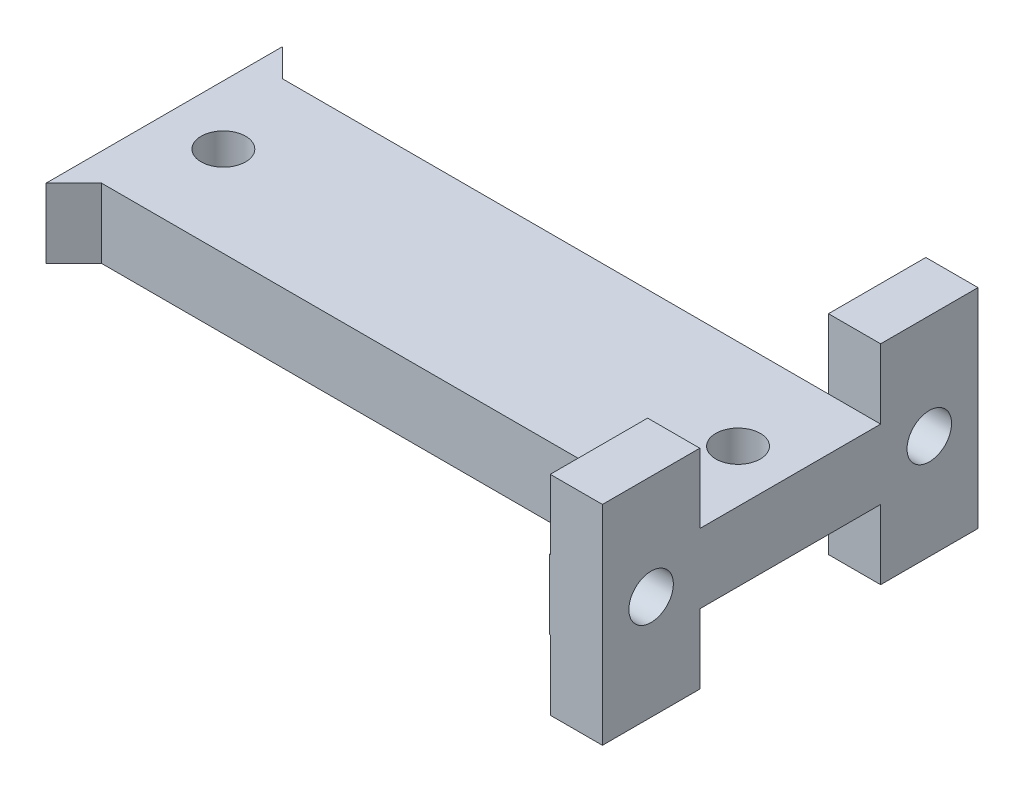
SolidWorks part; units mm, degrees
ref_plane "前视基准面" through (0, 0, 0) normal (0, 0, 1) x (1, 0, 0)
ref_plane "上视基准面" through (0, 0, 0) normal (0, 1, 0) x (1, 0, 0)
ref_plane "右视基准面" through (0, 0, 0) normal (1, 0, 0) x (0, 0, -1)
sketch "草图1" plane through (0, 0, 0) normal (0, 1, 0) x (1, 0, 0)
  line L0 (0, 0) -> (0, -100)
  line L1 (0, 0) -> (100, 0)
  line L2 (100, 0) -> (100, -100)
  line L3 (100, -100) -> (0, -100)
  dimension "D1" = 100
extrude "凸台-拉伸1" add sketch "草图1" along normal blind 10
sketch "草图2" plane through (0, 10, 0) normal (0, 1, 0) x (1, 0, 0)
  line L0 (20.6546, -10.25) -> (20.6546, -13)
  line L1 (20.6546, -13) -> (50.1546, -13)
  line L2 (50.1546, -13) -> (50.1546, -10.25)
  line L3 (50.1546, -10.25) -> (53.9046, -10.25)
  line L4 (16.9046, -2.75) -> (20.6546, -2.75)
  line L5 (20.6546, -2.75) -> (20.6546, 0)
  line L6 (100, 0) -> (0, 0) construction
  line L7 (20.6546, 0) -> (20.6546, -2.75) construction
  line L8 (20.6546, 0) -> (50, 0)
  line L9 (50, 0) -> (50.1546, -2.75)
  line L10 (50.1546, -2.75) -> (53.9046, -2.75)
  line L11 (16.9046, -10.25) -> (20.6546, -10.25)
  line L12 (20.6546, 0) -> (0, 0)
  line L13 (0, 0) -> (0, -100)
  line L14 (0, -100) -> (100, -100)
  line L15 (100, -100) -> (100, 0)
  line L16 (100, 0) -> (50, 0)
  line L17 (20.6546, -13) -> (0, -13)
  line L18 (50.1546, -13) -> (100, -13)
  line L19 (100, -13) -> (100, -100)
  arc A0 (53.9046, -10.25) -> (53.9046, -2.75) centre (53.9046, -6.5) ccw
  arc A1 (16.9046, -2.75) -> (16.9046, -10.25) centre (16.9046, -6.5) ccw
  line M3 (0, -100) -> (100, -100)
  line M4 (100, -100) -> (100, 0)
extrude "切除-拉伸3" cut sketch "草图2" against normal blind 27 contours L18 L1 L17 L13 M3 M4 region at (50, 10, 56.5)
sketch "草图4" plane through (0, 10, 0) normal (0, 1, 0) x (1, 0, 0)
  line L0 (16.9046, -6.5) -> (13.1546, -6.5)
  line L1 (13.1546, -6.5) -> (13.1546, 0)
  line L2 (100, 0) -> (0, 0) construction
  line L3 (13.1546, 0) -> (13.1546, -13)
  line L4 (0, -13) -> (100, -13) construction
  line L5 (53.9046, -6.5) -> (57.6546, -6.5)
  line L6 (57.6546, -6.5) -> (57.6546, -13)
  line L7 (57.6546, -13) -> (57.6546, 0)
  line L8 (57.6546, 0) -> (100, 0)
  line L9 (100, 0) -> (100, -13)
  line L10 (100, -13) -> (57.6546, -13)
  line L11 (13.1546, -13) -> (0, -13)
  line L12 (0, -13) -> (0, 0)
  line L13 (0, 0) -> (13.1546, 0)
  arc A0 (16.9046, -2.75) -> (16.9046, -10.25) centre (16.9046, -6.5) ccw construction
  arc A1 (53.9046, -10.25) -> (53.9046, -2.75) centre (53.9046, -6.5) ccw construction
  line M1 (0, -13) -> (100, -13)
  line M2 (100, -13) -> (100, 0)
  line M3 (100, 0) -> (0, 0)
  line M4 (0, 0) -> (0, -13)
extrude "切除-拉伸4" cut sketch "草图4" against normal blind 27 contours L3 L1 M3 M4 M1 | L7 L6 M1 M2 M3 region at (6.5773, 10, 6.5) region at (78.8273, 10, 6.5)
sketch "草图5" plane through (0, 10, 0) normal (0, 1, 0) x (1, 0, 0)
  circle A0 centre (16.9046, -6.5) radius 1.6
  circle A1 centre (53.9046, -6.5) radius 1.6
extrude "切除-拉伸5" cut sketch "草图5" against normal blind 27
sketch "草图6" plane through (0, 0, 13) normal (0, 0, 1) x (1, 0, 0)
  line L0 (50.1546, 10) -> (50.1546, 0)
  line L1 (13.1546, 10) -> (57.6546, 10) construction
  line L2 (50.1546, 17.2) -> (50.1546, 10) construction
  line L3 (57.6546, 0) -> (13.1546, 0) construction
  line L4 (50.1546, 5) -> (13.1546, 5)
  line L5 (13.1546, 10) -> (13.1546, 0) construction
  line L6 (13.1546, 5) -> (13.1546, 0)
  line L7 (13.1546, 0) -> (50.1546, 0)
  line L8 (50.1546, 5) -> (57.6546, 5)
  line L9 (57.6546, 0) -> (57.6546, 10) construction
  line L10 (57.6546, 5) -> (57.6546, 0)
  line L11 (57.6546, 0) -> (50.1546, 0)
  line M2 (13.1546, 10) -> (13.1546, 0)
  line M3 (13.1546, 0) -> (57.6546, 0)
  line M4 (57.6546, 0) -> (57.6546, 10)
extrude "切除-拉伸6" cut sketch "草图6" against normal blind 27 contours L0 L4 M2 M3 | L8 L0 M3 M4 region at (53.9046, 2.5, 13) region at (31.6546, 2.5, 13)
sketch "草图7" plane through (0, 10, 0) normal (0, 1, 0) x (1, 0, 0)
  line L0 (53.9046, -6.5) -> (53.9046, -13)
  line L1 (13.1546, -13) -> (57.6546, -13) construction
sketch "草图8" plane through (0, 0, 13) normal (0, 0, 1) x (1, 0, 0)
  line L0 (53.8487, 10) -> (53.8487, 5)
  line L1 (13.1546, 10) -> (57.6546, 10) construction
  line L2 (57.6546, 5) -> (13.1546, 5) construction
  line L3 (53.8487, 5) -> (57.6546, 5)
  line L4 (57.6546, 5) -> (57.6546, 10)
  line L5 (57.6546, 10) -> (53.8487, 10)
extrude "凸台-拉伸2" add sketch "草图8" along normal blind 7
sketch "草图9" plane through (0, 10, 0) normal (0, 1, 0) x (1, 0, 0)
  line L0 (53.9046, -6.5) -> (53.9046, 0)
  line L1 (57.6546, 0) -> (13.1546, 0) construction
sketch "草图10" plane through (0, 0, 0) normal (0, 0, -1) x (-1, 0, 0)
  line L0 (-53.9046, 10) -> (-53.9046, 5)
  line L1 (-57.6546, 5) -> (-13.1546, 5) construction
  line L2 (-53.9046, 5) -> (-57.6546, 5)
  line L3 (-57.6546, 5) -> (-57.6546, 10)
  line L4 (-57.6546, 10) -> (-53.9046, 10)
extrude "凸台-拉伸3" add sketch "草图10" along normal blind 7
sketch "草图11" plane through (13.1546, 0, 0) normal (-1, 0, 0) x (0, 0, 1)
  line L0 (6.5, 10) -> (6.5, 5)
  line L1 (6.5, 10) -> (13, 10) construction
  line L2 (6.5, 10) -> (0, 10) construction
  line L3 (0, 5) -> (13, 5) construction
sketch "草图14" plane through (57.6546, 0, 0) normal (1, 0, 0) x (0, 0, -1)
  line L0 (-13, 10) -> (-20, 10)
  line L1 (-20, 10) -> (-20, 15)
  line L2 (-20, 15) -> (-13, 15)
  line L3 (-13, 15) -> (-13, 10)
  line L4 (-20, 5) -> (-20, 0)
  line L5 (-20, 0) -> (-13, 0)
  line L6 (-13, 0) -> (-13, 5)
  line L7 (-13, 5) -> (-20, 5)
  line L8 (0, 10) -> (0, 15)
  line L9 (0, 10) -> (7, 10)
  line L10 (7, 10) -> (7, 15)
  line L11 (7, 15) -> (0, 15)
  line L12 (0, 5) -> (7, 5)
  line L13 (7, 5) -> (7, 0)
  line L14 (7, 0) -> (0, 0)
  line L15 (0, 0) -> (0, 5)
extrude "凸台-拉伸6" add sketch "草图14" against normal up to vertex (3.75 mm away) up to point (53.9046, 10, -7)
sketch "草图15" plane through (53.8487, 0, 0) normal (-1, 0, 0) x (0, 0, 1)
  line L0 (13, 10) -> (20, 5)
  line L1 (6.5, 10) -> (13, 10) construction
  line L2 (13, 10) -> (13, 5) construction
  line L3 (0, 10) -> (0, 5)
  line L4 (0, 5) -> (-7, 5)
  line L5 (-7, 0) -> (-7, 15) construction
  line L6 (-7, 5) -> (-7, 10)
  line L7 (-7, 10) -> (0, 10)
  line L8 (-7, 5) -> (0, 10)
  circle A0 centre (16.5, 7.5) radius 1.6
  circle A1 centre (-3.5, 7.5) radius 1.6
extrude "切除-拉伸8" cut sketch "草图15" against normal up to vertex (3.8059 mm away) contours L8 A1 | L8 A1 | L0 A0 | L0 A0 region at (53.8487, 8.0526, 16.8947) region at (53.8487, 6.9474, 16.1053) region at (53.8487, 6.9474, -3.1053) region at (53.8487, 8.0526, -3.8947) up to point (57.6546, 15, -7)
sketch "草图16" plane through (0, 10, 0) normal (0, 1, 0) x (1, 0, 0)
  line L0 (13.1546, 0) -> (12.6546, 0)
  line L1 (12.6546, 0) -> (12.6546, -13)
  line L2 (13.1546, -13) -> (12.6546, -13)
  line L3 (13.1546, 0) -> (13.1546, -13)
  dimension "D1" = 0.5
extrude "凸台-拉伸7" add sketch "草图16" against normal up to vertex (5 mm away) up to point (13.1546, 5, 13)
sketch "草图17" plane through (0, 5, 0) normal (0, -1, 0) x (1, 0, 0)
  line L0 (12.6546, 13) -> (12.6546, 15)
  line L1 (12.6546, 15) -> (14.6546, 13)
  line L2 (14.6546, 13) -> (12.6546, 13)
  line L3 (53.8487, 13) -> (12.6546, 13) construction
  line L5 (14.6546, 0) -> (12.6546, 0)
  line L6 (12.6546, -2) -> (14.6546, 0)
  line L7 (12.6546, 0) -> (12.6546, -2)
  dimension "D1" = 45
extrude "凸台-拉伸8" add sketch "草图17" against normal up to vertex (5 mm away) up to point (12.6546, 10, 13)
sketch "草图18" plane through (57.6546, 0, 0) normal (1, 0, 0) x (0, 0, -1)
  line L0 (-13, 10) -> (-6.5, 5)
  line L1 (-6.5, 10) -> (-13, 10) construction
  line L2 (-6.5, 5) -> (0, 10)
  circle A0 centre (-9.75, 7.5) radius 1.6
  circle A1 centre (-3.25, 7.5) radius 1.6
extrude "切除-拉伸9" cut sketch "草图18" along normal blind 10 from surface contours A0 | A1 starting at face at (12.6546, 7.5, 6.5)
